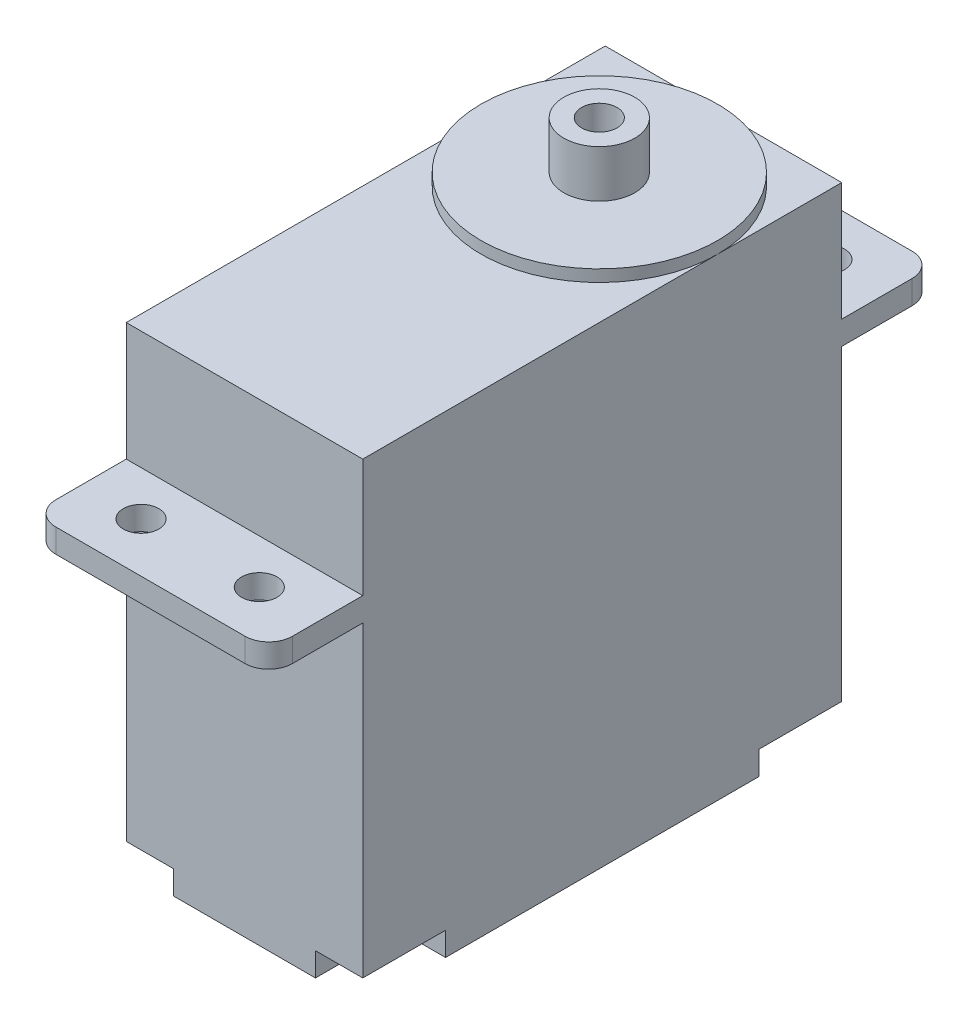
SolidWorks part; units mm, degrees
ref_plane "Front Plane" through (0, 0, 0) normal (0, 0, 1) x (1, 0, 0)
ref_plane "Top Plane" through (0, 0, 0) normal (0, 1, 0) x (1, 0, 0)
ref_plane "Right Plane" through (0, 0, 0) normal (1, 0, 0) x (0, 0, -1)
sketch "Sketch2" plane through (0, 77, 0) normal (0, 1, 0) x (1, 0, 0)
  line L1 (-49.2826, 255.8952) -> (-29.2826, 255.8952)
  line L2 (-49.2826, 255.8952) -> (-49.2826, 296.3952)
  line L3 (-49.2826, 296.3952) -> (-29.2826, 296.3952)
  line L4 (-29.2826, 255.8952) -> (-29.2826, 296.3952)
  dimension "D1" = 40.5
  dimension "D2" = 20
extrude "Boss-Extrude1" add sketch "Sketch2" along normal blind 28
sketch "Sketch3" plane through (0, 105, 0) normal (0, 1, 0) x (1, 0, 0)
  line L0 (-49.2826, 296.3952) -> (-49.2826, 255.8952) construction
  line L1 (-49.2826, 247.9452) -> (-29.2826, 247.9452)
  line L2 (-49.2826, 247.9452) -> (-49.2826, 304.3452)
  line L3 (-49.2826, 304.3452) -> (-29.2826, 304.3452)
  line L4 (-29.2826, 247.9452) -> (-29.2826, 304.3452)
  line L5 (-29.2826, 255.8952) -> (-29.2826, 296.3952) construction
  line L6 (-39.2826, 255.8952) -> (-39.2826, 296.3952) construction
  line L7 (-49.2826, 255.8952) -> (-29.2826, 255.8952) construction
  line L8 (-29.2826, 296.3952) -> (-49.2826, 296.3952) construction
  line L9 (-39.2826, 276.1452) -> (-34.2441, 276.1452) construction
  dimension "D1" = 0
  dimension "D2" = 0
  dimension "D3" = 56.4
  dimension "D4" = 28.2
extrude "Boss-Extrude2" add sketch "Sketch3" along normal blind 2
sketch "Sketch4" plane through (0, 107, 0) normal (0, 1, 0) x (1, 0, 0)
  line L4 (-49.2826, 296.3952) -> (-49.2826, 255.8952)
  line L5 (-29.2826, 296.3952) -> (-49.2826, 296.3952)
  line L6 (-29.2826, 255.8952) -> (-29.2826, 296.3952)
  line L7 (-49.2826, 255.8952) -> (-29.2826, 255.8952)
  line L8 (-49.2826, 296.3952) -> (-49.2826, 255.8952)
  line L9 (-29.2826, 296.3952) -> (-49.2826, 296.3952)
  line L10 (-29.2826, 255.8952) -> (-29.2826, 296.3952)
  line L11 (-49.2826, 255.8952) -> (-29.2826, 255.8952)
  dimension "D1" = 0
extrude "Boss-Extrude3" add sketch "Sketch4" along normal blind 10
sketch "Sketch5" plane through (0, 117, 0) normal (0, 1, 0) x (1, 0, 0)
  line L0 (-29.2826, 255.8952) -> (-29.2826, 296.3952) construction
  line L1 (-49.2826, 296.3952) -> (-49.2826, 255.8952) construction
  line L2 (-49.2826, 255.8952) -> (-29.2826, 255.8952) construction
  circle A0 centre (-39.2826, 285.8952) radius 10
  dimension "D1" = 30
extrude "Boss-Extrude4" add sketch "Sketch5" along normal blind 1
sketch "Sketch6" plane through (0, 118, 0) normal (0, 1, 0) x (1, 0, 0)
  circle A0 centre (-39.2826, 285.8952) radius 3
  circle A1 centre (-39.2826, 285.8952) radius 1.5
extrude "Boss-Extrude5" add sketch "Sketch6" along normal blind 4
sketch "Sketch7" plane through (0, 107, 0) normal (0, 1, 0) x (1, 0, 0)
  line L0 (-39.2826, 247.9452) -> (-39.2826, 304.3452) construction
  line L1 (-49.2826, 247.9452) -> (-29.2826, 247.9452) construction
  line L2 (-29.2826, 304.3452) -> (-49.2826, 304.3452) construction
  line L3 (-39.2826, 276.1452) -> (-49.2826, 276.1452) construction
  line L4 (-49.2826, 285.8952) -> (-49.2826, 255.8952) construction
  circle A0 centre (-44.2826, 252.1452) radius 1.5
  circle A1 centre (-34.2826, 252.1452) radius 1.5
  circle A2 centre (-34.2826, 300.1452) radius 1.5
  circle A3 centre (-44.2826, 300.1452) radius 1.5
  dimension "D1" = 5
  dimension "D2" = 24
extrude "Cut-Extrude1" cut sketch "Sketch7" against normal blind 2
fillet "Fillet1" radius 2 4 edges at (-29.2826, 106, -304.3452) (-49.2826, 106, -304.3452) (-49.2826, 106, -247.9452) (-29.2826, 106, -247.9452)
sketch "Sketch8" plane through (0, 77, 0) normal (0, -1, 0) x (1, 0, 0)
  line L0 (-39.2826, -255.8952) -> (-39.2826, -296.3952) construction
  line L1 (-29.2826, -255.8952) -> (-33.2826, -255.8952)
  line L2 (-29.2826, -255.8952) -> (-29.2826, -262.8952)
  line L3 (-29.2826, -262.8952) -> (-33.2826, -262.8952)
  line L4 (-33.2826, -255.8952) -> (-33.2826, -262.8952)
  line L5 (-49.2826, -255.8952) -> (-29.2826, -255.8952) construction
  line L6 (-29.2826, -296.3952) -> (-49.2826, -296.3952) construction
  line L7 (-29.2826, -276.1452) -> (-49.2826, -276.1452) construction
  line L8 (-29.2826, -255.8952) -> (-29.2826, -296.3952) construction
  line L9 (-49.2826, -296.3952) -> (-49.2826, -255.8952) construction
  line L10 (-33.2826, -296.3952) -> (-33.2826, -289.3952)
  line L11 (-29.2826, -289.3952) -> (-33.2826, -289.3952)
  line L12 (-29.2826, -296.3952) -> (-29.2826, -289.3952)
  line L13 (-29.2826, -296.3952) -> (-33.2826, -296.3952)
  line L14 (-49.2826, -296.3952) -> (-45.2826, -296.3952)
  line L15 (-49.2826, -296.3952) -> (-49.2826, -289.3952)
  line L16 (-49.2826, -289.3952) -> (-45.2826, -289.3952)
  line L17 (-45.2826, -296.3952) -> (-45.2826, -289.3952)
  line L18 (-45.2826, -255.8952) -> (-45.2826, -262.8952)
  line L19 (-49.2826, -262.8952) -> (-45.2826, -262.8952)
  line L20 (-49.2826, -255.8952) -> (-49.2826, -262.8952)
  line L21 (-49.2826, -255.8952) -> (-45.2826, -255.8952)
extrude "Cut-Extrude2" cut sketch "Sketch8" against normal blind 2
sketch "Sketch9" plane through (0, 0, -296.3952) normal (0, 0, -1) x (-1, 0, 0)
  line L0 (33.2826, 77) -> (45.2826, 77) construction
  line L1 (35.2826, 77) -> (43.2826, 77)
  line L2 (35.2826, 77) -> (35.2826, 80)
  line L3 (35.2826, 80) -> (43.2826, 80)
  line L4 (43.2826, 77) -> (43.2826, 80)
  line L5 (39.2826, 122) -> (39.2826, 77) construction
  line L6 (42.2826, 122) -> (36.2826, 122) construction
  point P10 (0, 0)
  dimension "D1" = 8
  dimension "D2" = 4
  dimension "D3" = 3
extrude "Boss-Extrude6" add sketch "Sketch9" along normal blind 5
